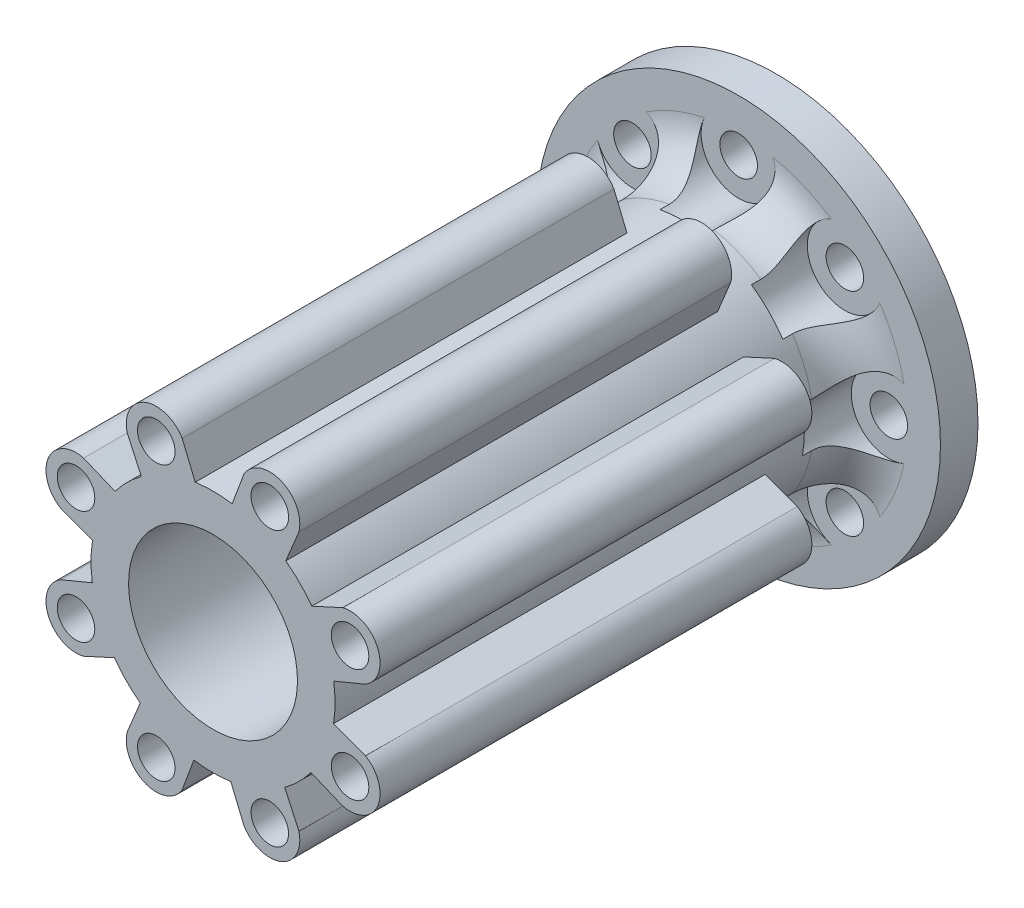
SolidWorks part; units mm, degrees
ref_plane "Alzado" through (0, 0, 0) normal (0, 0, 1) x (1, 0, 0)
ref_plane "Planta" through (0, 0, 0) normal (0, 1, 0) x (1, 0, 0)
ref_plane "Vista lateral" through (0, 0, 0) normal (1, 0, 0) x (0, 0, -1)
sketch "Croquis1" plane through (0, 0, 0) normal (0, 0, 1) x (1, 0, 0)
  circle A0 centre (0, 0) radius 9.5
  circle A1 centre (0, 0) radius 4.5
  dimension "D1" = 19
  dimension "D2" = 9
extrude "Saliente-Extruir1" add sketch "Croquis1" along normal blind 2
sketch "Croquis2" plane through (0, 0, 2) normal (0, 0, 1) x (1, 0, 0)
  arc A0 (-0.8, -8) -> (0.8, -8) centre (0, -8) ccw construction
  arc A3 (-6.2225, -5.0912) -> (-5.0912, -6.2225) centre (-5.6569, -5.6569) ccw construction
  arc A4 (-8, 0.8) -> (-8, -0.8) centre (-8, 0) ccw construction
  arc A5 (-5.0912, 6.2225) -> (-6.2225, 5.0912) centre (-5.6569, 5.6569) ccw construction
  arc A6 (5.0912, -6.2225) -> (6.2225, -5.0912) centre (5.6569, -5.6569) ccw construction
  arc A7 (8, -0.8) -> (8, 0.8) centre (8, 0) ccw construction
  arc A8 (0.8, 8) -> (-0.8, 8) centre (0, 8) ccw construction
  arc A9 (6.2225, 5.0912) -> (5.0912, 6.2225) centre (5.6569, 5.6569) ccw construction
  circle A10 centre (0, -8) radius 0.8
  circle A11 centre (-5.6569, -5.6569) radius 0.8
  circle A12 centre (-8, 0) radius 0.8
  circle A13 centre (-5.6569, 5.6569) radius 0.8
  circle A14 centre (5.6569, -5.6569) radius 0.8
  circle A15 centre (8, 0) radius 0.8
  circle A16 centre (0, 8) radius 0.8
  circle A17 centre (5.6569, 5.6569) radius 0.8
extrude "Cortar-Extruir3" cut sketch "Croquis2" against normal blind 2
sketch "Croquis3" plane through (0, 0, 2) normal (0, 0, 1) x (1, 0, 0)
  circle A0 centre (0, 0) radius 4.5
  circle A1 centre (0, 0) radius 6.5
  dimension "D1" = 9
  dimension "D2" = 13
extrude "Saliente-Extruir2" add sketch "Croquis3" along normal up to surface (28 mm away)
sketch "Croquis4" plane through (0, 0, 30) normal (0, 0, 1) x (1, 0, 0)
  line L0 (0, 0) -> (8.7769, 3.6355) construction
  line L1 (6.4305, 0.9482) -> (8.1085, 1.6433)
  line L2 (5.2597, 3.8191) -> (6.911, 4.5755)
  line L3 (5.2175, -3.8765) -> (6.8956, -4.5716)
  line L4 (6.4197, -1.0186) -> (8.1222, -1.6514)
  line L5 (0.9482, -6.4305) -> (1.6433, -8.1085)
  line L6 (3.8191, -5.2597) -> (4.5755, -6.911)
  line L7 (-3.8765, -5.2175) -> (-4.5716, -6.8956)
  line L8 (-1.0186, -6.4197) -> (-1.6514, -8.1222)
  line L9 (-6.4305, -0.9482) -> (-8.1085, -1.6433)
  line L10 (-5.2597, -3.8191) -> (-6.911, -4.5755)
  line L11 (-5.2175, 3.8765) -> (-6.8956, 4.5716)
  line L12 (-6.4197, 1.0186) -> (-8.1222, 1.6514)
  line L13 (-0.9482, 6.4305) -> (-1.6433, 8.1085)
  line L14 (-3.8191, 5.2597) -> (-4.5755, 6.911)
  line L15 (3.8765, 5.2175) -> (4.5716, 6.8956)
  line L16 (1.0186, 6.4197) -> (1.6514, 8.1222)
  circle A0 centre (0, 0) radius 9.5 construction
  arc A1 (8.1085, 1.6433) -> (6.911, 4.5755) centre (7.2986, 3.0232) ccw
  circle A2 centre (0, 0) radius 6.5 construction
  arc A3 (5.2597, 3.8191) -> (6.4305, 0.9482) centre (0, 0) cw
  arc A5 (6.8956, -4.5716) -> (8.1222, -1.6514) centre (7.2986, -3.0232) ccw
  arc A6 (6.4197, -1.0186) -> (5.2175, -3.8765) centre (0, 0) cw
  arc A8 (1.6433, -8.1085) -> (4.5755, -6.911) centre (3.0232, -7.2986) ccw
  arc A9 (3.8191, -5.2597) -> (0.9482, -6.4305) centre (0, 0) cw
  arc A11 (-4.5716, -6.8956) -> (-1.6514, -8.1222) centre (-3.0232, -7.2986) ccw
  arc A12 (-1.0186, -6.4197) -> (-3.8765, -5.2175) centre (0, 0) cw
  arc A14 (-8.1085, -1.6433) -> (-6.911, -4.5755) centre (-7.2986, -3.0232) ccw
  arc A15 (-5.2597, -3.8191) -> (-6.4305, -0.9482) centre (0, 0) cw
  arc A17 (-6.8956, 4.5716) -> (-8.1222, 1.6514) centre (-7.2986, 3.0232) ccw
  arc A18 (-6.4197, 1.0186) -> (-5.2175, 3.8765) centre (0, 0) cw
  arc A20 (-1.6433, 8.1085) -> (-4.5755, 6.911) centre (-3.0232, 7.2986) ccw
  arc A21 (-3.8191, 5.2597) -> (-0.9482, 6.4305) centre (0, 0) cw
  arc A23 (4.5716, 6.8956) -> (1.6514, 8.1222) centre (3.0232, 7.2986) ccw
  arc A24 (1.0186, 6.4197) -> (3.8765, 5.2175) centre (0, 0) cw
  point P57 (0, 0)
  dimension "D1" = 3.2
  dimension "D3" = 3.0232
  dimension "D2" = 2.11
  dimension "D4" = 1.5848
  dimension "D6" = 8
extrude "Saliente-Extruir3" add sketch "Croquis4" against normal up to surface (28 mm away) up to face at (9.5, 0, 2)
sketch "Croquis5" plane through (0, 0, 30) normal (0, 0, 1) x (1, 0, 0)
  circle A0 centre (-3.0232, 7.2986) radius 1
  circle A1 centre (3.0232, 7.2986) radius 1
  circle A2 centre (7.2986, 3.0232) radius 1
  circle A3 centre (7.2986, -3.0232) radius 1
  circle A4 centre (3.0232, -7.2986) radius 1
  circle A5 centre (-3.0232, -7.2986) radius 1
  circle A6 centre (-7.2986, -3.0232) radius 1
  circle A7 centre (-7.2986, 3.0232) radius 1
  point P20 (0, 0)
  dimension "D1" = 2
  dimension "D2" = 8
extrude "Cortar-Extruir4" cut sketch "Croquis5" against normal blind 5
sketch "Croquis6" plane through (0, 0, 0) normal (0, 0, -1) x (-1, 0, 0)
  circle A0 centre (0, 0) radius 10.75
  circle A1 centre (0, 0) radius 4.5
  circle A2 centre (8, 0) radius 0.8 construction
  circle A3 centre (5.6569, -5.6569) radius 0.8 construction
  circle A4 centre (0, -8) radius 0.8 construction
  circle A5 centre (-5.6569, -5.6569) radius 0.8 construction
  circle A6 centre (-8, 0) radius 0.8 construction
  circle A7 centre (-5.6569, 5.6569) radius 0.8 construction
  circle A8 centre (0, 8) radius 0.8 construction
  circle A9 centre (5.6569, 5.6569) radius 0.8 construction
  circle A10 centre (8, 0) radius 0.8
  circle A11 centre (5.6569, -5.6569) radius 0.8
  circle A12 centre (0, -8) radius 0.8
  circle A13 centre (-5.6569, -5.6569) radius 0.8
  circle A14 centre (-8, 0) radius 0.8
  circle A15 centre (-5.6569, 5.6569) radius 0.8
  circle A16 centre (0, 8) radius 0.8
  circle A17 centre (5.6569, 5.6569) radius 0.8
  dimension "D1" = 21.5
  dimension "D2" = 9
extrude "Saliente-Extruir4" add sketch "Croquis6" against normal up to surface (2 mm away) up to face at (5.6871, 5.6676, 2)
sketch "Croquis7" plane through (0, 0, 2) normal (0, 0, 1) x (1, 0, 0)
  circle A0 centre (-8, 0) radius 0.8 construction
  circle A1 centre (-5.6569, -5.6569) radius 0.8 construction
  circle A2 centre (0, -8) radius 0.8 construction
  circle A3 centre (5.6569, -5.6569) radius 0.8 construction
  circle A4 centre (8, 0) radius 0.8 construction
  circle A5 centre (5.6569, 5.6569) radius 0.8 construction
  circle A6 centre (0, 8) radius 0.8 construction
  circle A7 centre (-5.6569, 5.6569) radius 0.8 construction
  circle A8 centre (-8, 0) radius 0.8 construction
  circle A9 centre (-5.6569, -5.6569) radius 0.8 construction
  circle A10 centre (0, -8) radius 0.8 construction
  circle A11 centre (5.6569, -5.6569) radius 0.8 construction
  circle A12 centre (8, 0) radius 0.8 construction
  circle A13 centre (5.6569, 5.6569) radius 0.8 construction
  circle A14 centre (0, 8) radius 0.8 construction
  circle A15 centre (-5.6569, 5.6569) radius 0.8 construction
  circle A16 centre (-5.6569, 5.6569) radius 1
  circle A17 centre (0, 8) radius 1
  circle A18 centre (5.6569, 5.6569) radius 1
  circle A19 centre (8, 0) radius 1
  circle A20 centre (5.6569, -5.6569) radius 1
  circle A21 centre (0, -8) radius 1
  circle A22 centre (-5.6569, -5.6569) radius 1
  circle A23 centre (-8, 0) radius 1
  dimension "D1" = 0.2
extrude "Cortar-Extruir5" cut sketch "Croquis7" against normal blind 10
sketch "Croquis8" plane through (0, 0, 2) normal (0, 0, 1) x (1, 0, 0)
  circle A0 centre (0, 0) radius 10.75
  circle A1 centre (0, 0) radius 6.5
  dimension "D1" = 21.5
  dimension "D2" = 13
extrude "Cortar-Extruir6" cut sketch "Croquis8" along normal blind 5
sketch "Croquis9" plane through (0, 0, 2) normal (0, 0, 1) x (1, 0, 0)
  circle A0 centre (5.6569, -5.6569) radius 1 construction
  circle A1 centre (0, -8) radius 1 construction
  circle A2 centre (-5.6569, -5.6569) radius 1 construction
  circle A3 centre (-8, 0) radius 1 construction
  circle A4 centre (-5.6569, 5.6569) radius 1 construction
  circle A5 centre (0, 8) radius 1 construction
  circle A6 centre (5.6569, 5.6569) radius 1 construction
  circle A7 centre (8, 0) radius 1 construction
  circle A8 centre (5.6569, -5.6569) radius 1 construction
  circle A9 centre (0, -8) radius 1 construction
  circle A10 centre (-5.6569, -5.6569) radius 1 construction
  circle A11 centre (-8, 0) radius 1 construction
  circle A12 centre (-5.6569, 5.6569) radius 1 construction
  circle A13 centre (0, 8) radius 1 construction
  circle A14 centre (5.6569, 5.6569) radius 1 construction
  circle A15 centre (8, 0) radius 1 construction
  circle A16 centre (0, -8) radius 2
  circle A17 centre (5.6569, -5.6569) radius 2
  circle A18 centre (8, 0) radius 2
  circle A19 centre (5.6569, 5.6569) radius 2
  circle A20 centre (0, 8) radius 2
  circle A21 centre (-5.6569, 5.6569) radius 2
  circle A22 centre (-8, 0) radius 2
  circle A23 centre (-5.6569, -5.6569) radius 2
  dimension "D1" = 1
extrude "Cortar-Extruir7" cut sketch "Croquis9" along normal blind 3
fillet "Redondeo1" radius 2.5 8 edges at (-6.0052, -2.4874, 2) (-6.0052, 2.4874, 2) (-2.4874, 6.0052, 2) (2.4874, 6.0052, 2) (6.0052, 2.4874, 2) (6.0052, -2.4874, 2) (2.4874, -6.0052, 2) (-2.4874, -6.0052, 2)
sketch "Croquis11" plane through (0, 0, 0) normal (0, 1, 0) x (1, 0, 0)
  line L0 (6.5, -30) -> (6.5, -5) construction
  circle A0 centre (0, -13) radius 3.25
  dimension "D2" = 6.5
  dimension "D1" = 13
  dimension "D3" = 6.5
extrude "Cortar-Extruir8" cut sketch "Croquis11" against normal blind 9
